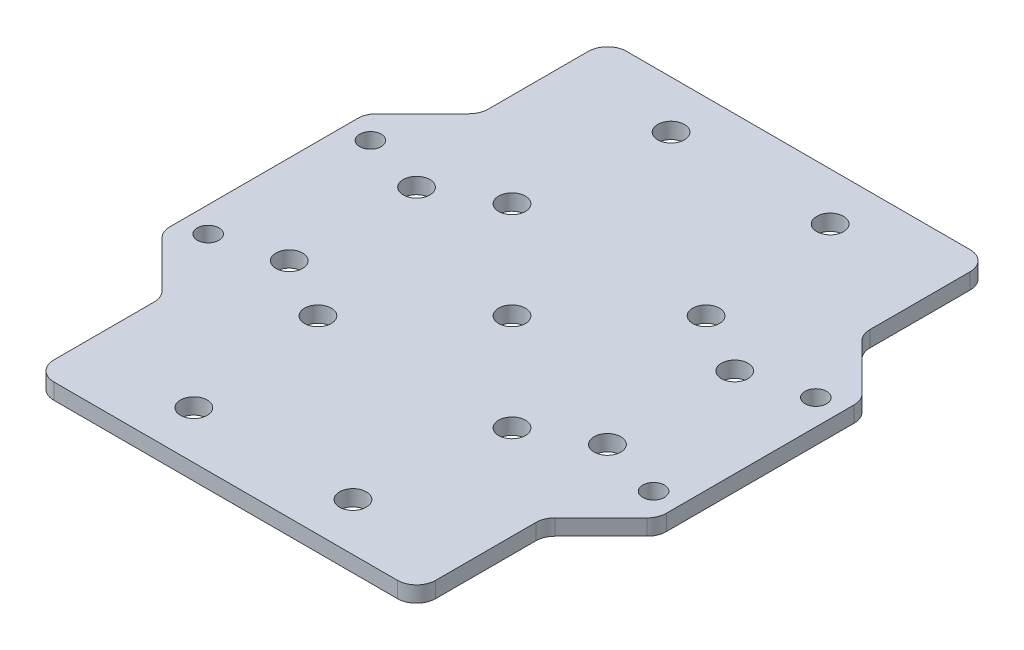
SolidWorks part; units mm, degrees
material "Thornel Mat VMA"
ref_plane "Front Plane" through (0, 0, 0) normal (0, 0, 1) x (1, 0, 0)
ref_plane "Top Plane" through (0, 0, 0) normal (0, 1, 0) x (1, 0, 0)
ref_plane "Right Plane" through (0, 0, 0) normal (1, 0, 0) x (0, 0, -1)
sketch "Sketch1" plane through (0, 0, 0) normal (0, 1, 0) x (1, 0, 0)
  line L0 (-30, 0) -> (-39, 0) construction
  line L1 (-30, 45) -> (30, 45)
  line L2 (-30, 45) -> (-30, -45)
  line L3 (-30, -45) -> (30, -45)
  line L4 (30, 45) -> (30, -45)
  line L5 (-30, 45) -> (30, -45) construction
  line L6 (-30, -45) -> (30, 45) construction
  line L7 (-15.25, -15.25) -> (15.25, -15.25) construction
  line L8 (-15.25, -15.25) -> (-15.25, 15.25) construction
  line L9 (-15.25, 15.25) -> (15.25, 15.25) construction
  line L10 (15.25, -15.25) -> (15.25, 15.25) construction
  line L11 (-15.25, -15.25) -> (15.25, 15.25) construction
  line L12 (-15.25, 15.25) -> (15.25, -15.25) construction
  line L13 (-39, -16) -> (-39, 16)
  line L14 (-39, 16) -> (-30, 25)
  line L15 (-39, -16) -> (-30, -25)
  line L16 (0, 0) -> (0, 36.025) construction
  line L17 (39, -16) -> (30, -25)
  line L18 (30, 0) -> (39, 0) construction
  line L19 (39, 16) -> (30, 25)
  line L20 (39, -16) -> (39, 16)
  point P0 (0, 0)
  point P6 (0, 0)
  dimension "D1" = 9
  dimension "56" = 60
  dimension "D2" = 30.5
  dimension "D3" = 90
  dimension "D4" = 16
  dimension "D5" = 45
extrude "Boss-Extrude1" add sketch "Sketch1" along normal mid plane 2.5 contours L1 | L4 L1 L2 L3 | L3 | L13 L15 L2 L14 | L17 L20 L19 L4 region at (0, 0, 0) region at (-34.1707, 0, 0) region at (34.1707, 0, 0)
fillet "Fillet1" radius 3 12 edges at (30, 0, -45) (30, 0, 45) (-30, 0, 45) (-30, 0, -45) (30, 0, 25) (39, 0, 16) (39, 0, -16) (30, 0, -25) (-39, 0, -16) (-30, 0, -25) (-39, 0, 16) (-30, 0, 25)
hole_wizard "Ø4.2 (4.2) Diameter Hole1" positions "Sketch3" profile "Sketch4" hole size "Ø4.2" standard "ANSI Metric" end condition through all
sketch "Sketch3" plane through (0, 1.25, 0) normal (0, 1, 0) x (1, 0, 0)
  line L1 (-15.25, 15.25) -> (15.25, 15.25) construction
  line L2 (-15.25, 15.25) -> (-15.25, -15.25) construction
  line L3 (-15.25, -15.25) -> (15.25, -15.25) construction
  line L4 (15.25, 15.25) -> (15.25, -15.25) construction
  line L5 (-15.25, 15.25) -> (15.25, -15.25) construction
  line L6 (-15.25, -15.25) -> (15.25, 15.25) construction
  point P0 (0, 0)
  point P4 (0, 0)
  point P5 (15.25, -15.25)
  point P50 (-15.25, 15.25)
  point P51 (-15.25, -15.25)
  point P52 (15.25, 15.25)
  dimension "D1" = 30.5
sketch "Sketch4" plane through (0, 1.25, 0) normal (1, 0, 0) x (0, 0, 1)
  line L0 (0, 0) -> (0, 2.5)
  line L1 (0, 2.5) -> (2.1, 2.5)
  line L2 (2.1, 2.5) -> (2.1, 0)
  line L5 (2.1, 0) -> (0, 0)
  line L11 (0, -6.35) -> (0, 107.95) construction
  dimension "Thru Hole Dia." = 4.2
  dimension "Thru Hole Depth" = 2.5
hole_wizard "M3 Clearance Hole1" positions "Sketch5" profile "Sketch6" hole size "M3" standard "ANSI Metric" end condition through all
sketch "Sketch5" plane through (0, 1.25, 0) normal (0, 1, 0) x (1, 0, 0)
  point P0 (35, 12.75)
  point P3 (35, -12.75)
  point P6 (-35, -12.75)
  point P9 (-35, 12.75)
sketch "Sketch6" plane through (35, 1.25, -12.75) normal (1, 0, 0) x (0, 0, 1)
  line L0 (0, 0) -> (0, 2.5)
  line L1 (0, 2.5) -> (1.7, 2.5)
  line L2 (1.7, 2.5) -> (1.7, 0)
  line L5 (1.7, 0) -> (0, 0)
  line L11 (0, -6.35) -> (0, 107.95) construction
  dimension "Thru Hole Dia." = 3.4
  dimension "Thru Hole Depth" = 2.5
hole_wizard "Ø4.2 (4.2) Diameter Hole2" positions "Sketch7" profile "Sketch8" hole size "Ø4.2" standard "ANSI Metric" end condition through all
sketch "Sketch7" plane through (0, -1.25, 0) normal (0, -1, 0) x (-1, 0, 0)
  point P0 (-12.5, 37.5)
  point P3 (-25, 10)
  point P6 (-25, -10)
  point P9 (-12.5, -37.5)
  point P12 (12.5, -37.5)
  point P15 (25, -10)
  point P18 (12.5, 37.5)
  point P27 (25, 10)
sketch "Sketch8" plane through (12.5, -1.25, -37.5) normal (1, 0, 0) x (0, 0, -1)
  line L0 (0, 0) -> (0, 2.5)
  line L1 (0, 2.5) -> (2.1, 2.5)
  line L2 (2.1, 2.5) -> (2.1, 0)
  line L5 (2.1, 0) -> (0, 0)
  line L11 (0, -6.35) -> (0, 107.95) construction
  dimension "Thru Hole Dia." = 4.2
  dimension "Thru Hole Depth" = 2.5
